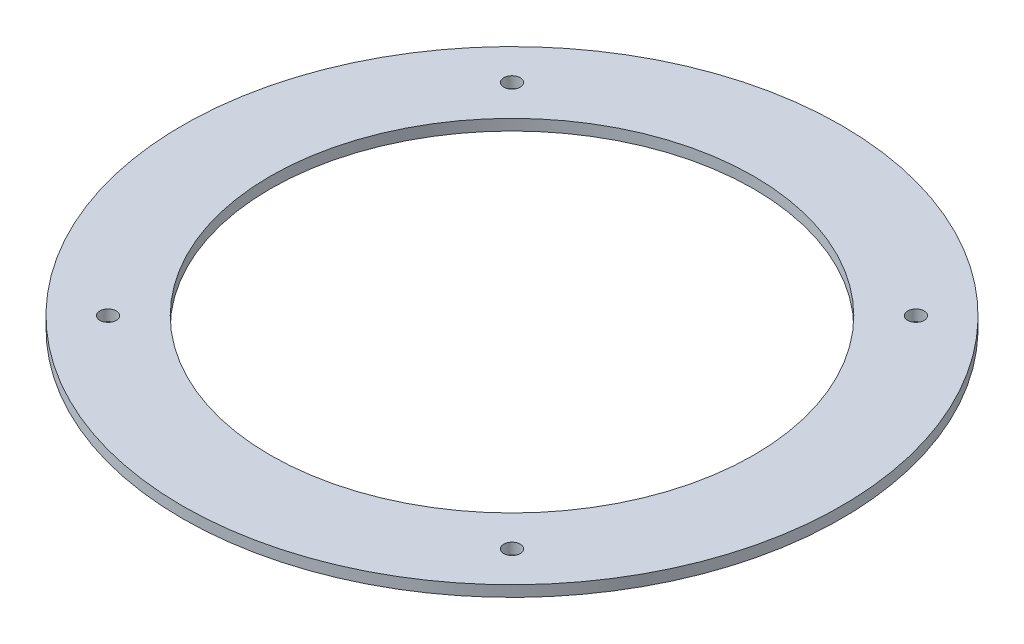
SolidWorks part; units mm, degrees
note: The reader was unsure of these and kept them because the rebuilt part matched: thickness of "基体-法兰1", "钣金6", "钣金7", "钣金8".
ref_plane "前视基准面" through (0, 0, 0) normal (0, 0, 1) x (1, 0, 0)
ref_plane "上视基准面" through (0, 0, 0) normal (0, 1, 0) x (1, 0, 0)
ref_plane "右视基准面" through (0, 0, 0) normal (1, 0, 0) x (0, 0, -1)
sketch "草图1" plane through (0, 0, 0) normal (0, 1, 0) x (1, 0, 0)
  circle A0 centre (0, 0) radius 60
  circle A2 centre (0, 0) radius 51
  dimension "D1" = 120
  dimension "D2" = 102
base flange "基体-法兰1" sketch "草图1" thickness 2 reverse thickness direction no parameters "D1"=0.7366
sketch "草图7" plane through (0, 0, 0) normal (0, 1, 0) x (1, 0, 0)
  circle A0 centre (0, 0) radius 44
  dimension "D1" = 88
extrude "切除-拉伸2" cut sketch "草图7" against normal up to next contours A0 normal cut yes
sketch "草图6" plane through (0, 0, 0) normal (0, 1, 0) x (1, 0, 0)
  line L0 (0, 60) -> (0, -60) construction
  line L1 (-60, 0) -> (60, 0) construction
  circle A7 centre (0, 0) radius 60 construction
  circle A8 centre (-36.7696, -36.7696) radius 1.5
  circle A9 centre (-36.7696, 36.7696) radius 1.5
  circle A10 centre (36.7696, 36.7696) radius 1.5
  circle A11 centre (36.7696, -36.7696) radius 1.5
  point P19 (0, 0)
  dimension "D1" = 3
  dimension "D2" = 4
  dimension "D5" = 52
extrude "切除-拉伸1" cut sketch "草图6" against normal up to next normal cut yes
sketch "折弯-线1" plane through (0, 0, 0) normal (0, 1, 0) x (1, 0, 0)
sketch "边界框1" plane through (0, 0, 0) normal (0, 1, 0) x (1, 0, 0)
sheet metal parameters "钣金6" thickness 2 parameters "D1"=0.7366
flat pattern "平板型式6" [suppressed]
sketch "折弯-线2" plane through (0, 0, 0) normal (0, 1, 0) x (1, 0, 0)
sketch "边界框2" [suppressed] plane through (0, 0, 0) normal (0, 1, 0) x (1, 0, 0)
sheet metal parameters "钣金7" thickness 2 parameters "D1"=0.7366, "D7"=3
flat pattern "平板型式6"
sketch "折弯-线2" plane through (0, 0, 0) normal (0, 1, 0) x (1, 0, 0)
sketch "边界框2" [suppressed] plane through (0, 0, 0) normal (0, 1, 0) x (1, 0, 0)
sheet metal parameters "钣金8" thickness 2 parameters "D1"=0.7366
flat pattern "平板型式6"
sketch "折弯-线2" plane through (0, 0, 0) normal (0, 1, 0) x (1, 0, 0)
sketch "边界框2" [suppressed] plane through (0, 0, 0) normal (0, 1, 0) x (1, 0, 0)
